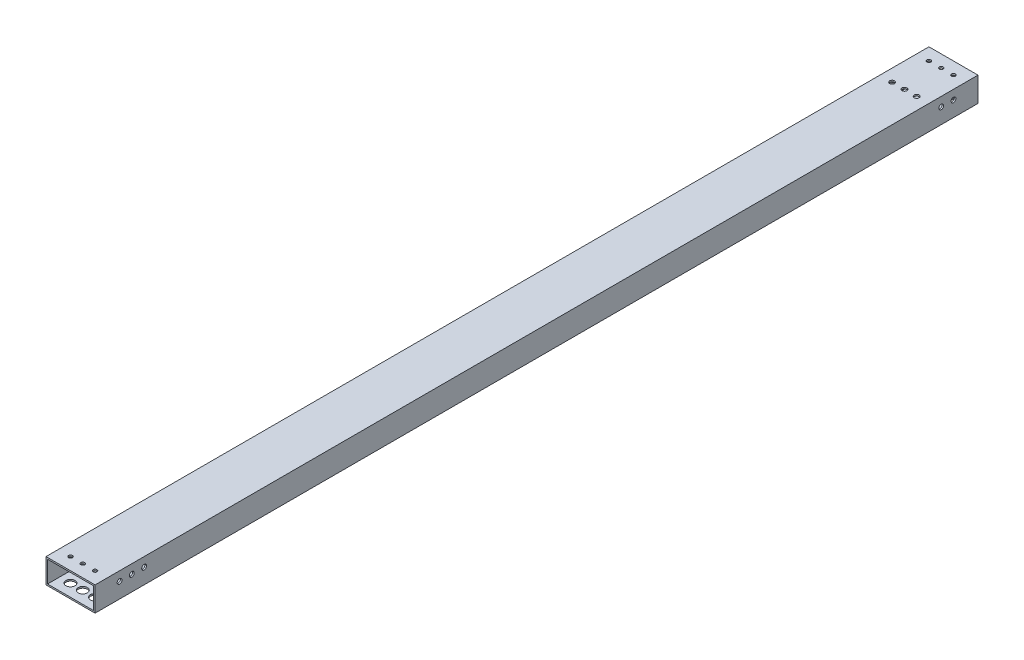
SolidWorks part; units mm, degrees
other "Markup1"
sketch "Sketch5" plane through (-25.4, -12.7, -457.2) normal (-0.35, -0.9329, -0.0852) x (-0.8023, 0.2515, 0.5413)
sketch "Sketch6" plane through (-25.4, -12.7, -457.2) normal (-0.35, -0.9329, -0.0852) x (-0.8023, 0.2515, 0.5413)
sketch "Sketch8" plane through (-25.4, -12.7, -457.2) normal (-0.35, -0.9329, -0.0852) x (-0.8023, 0.2515, 0.5413)
sketch "Sketch9" plane through (-25.4, -12.7, -457.2) normal (-0.35, -0.9329, -0.0852) x (-0.8023, 0.2515, 0.5413)
sketch "Sketch11" plane through (-25.4, -12.7, -457.2) normal (-0.35, -0.9329, -0.0852) x (-0.8023, 0.2515, 0.5413)
sketch "Sketch13" plane through (-25.4, -12.7, -457.2) normal (-0.35, -0.9329, -0.0852) x (-0.8023, 0.2515, 0.5413)
material "6061-T6 (SS)"
ref_plane "Front Plane" through (0, 0, 0) normal (0, 0, 1) x (1, 0, 0)
ref_plane "Top Plane" through (0, 0, 0) normal (0, 1, 0) x (1, 0, 0)
ref_plane "Right Plane" through (0, 0, 0) normal (1, 0, 0) x (0, 0, -1)
sketch "Sketch1" plane through (0, 0, 0) normal (0, 0, 1) x (1, 0, 0)
  line L0 (-23.8125, 11.1125) -> (23.8125, 11.1125)
  line L1 (-25.4, -12.7) -> (25.4, -12.7)
  line L2 (-25.4, -12.7) -> (-25.4, 12.7)
  line L3 (-25.4, 12.7) -> (25.4, 12.7)
  line L4 (25.4, -12.7) -> (25.4, 12.7)
  line L5 (-25.4, -12.7) -> (25.4, 12.7) construction
  line L6 (-25.4, 12.7) -> (25.4, -12.7) construction
  line L7 (23.8125, -11.1125) -> (23.8125, 11.1125)
  line L8 (-23.8125, -11.1125) -> (23.8125, -11.1125)
  line L9 (-23.8125, -11.1125) -> (-23.8125, 11.1125)
  point P0 (0, 0)
  dimension "D1" = 50.8
  dimension "D2" = 25.4
  dimension "D3" = 1.5875
extrude "Boss-Extrude1" add sketch "Sketch1" along normal mid plane 914.4
sketch "Sketch3" plane through (0, 12.7, 0) normal (0, 1, 0) x (1, 0, 0)
  line L2 (25.4, -457.2) -> (-25.4, -457.2) construction
  line L3 (25.4, 0) -> (-25.4, 0) construction
  line L4 (25.4, -457.2) -> (25.4, 457.2) construction
  line L5 (-25.4, -457.2) -> (-25.4, 457.2) construction
  circle A0 centre (0, -444.5) radius 2.0193
  circle A1 centre (12.7, -444.5) radius 2.0193
  circle A2 centre (-12.7, -444.5) radius 2.0193
  circle A3 centre (12.7, 444.5) radius 2.0193
  circle A4 centre (0, 444.5) radius 2.0193
  circle A5 centre (-12.7, 444.5) radius 2.0193
  dimension "D1" = 4.0386
  dimension "D2" = 12.7
  dimension "D3" = 12.7
  dimension "D4" = 12.7
extrude "Cut-Extrude2" cut sketch "Sketch3" against normal up to surface (1.5875 mm away) up to face at (0, 11.1125, 0)
sketch "Sketch4" plane through (0, -12.7, 0) normal (0, -1, 0) x (1, 0, 0)
  circle A0 centre (-12.7, 444.5) radius 2.0193 construction
  circle A1 centre (0, 444.5) radius 2.0193 construction
  circle A2 centre (12.7, 444.5) radius 2.0193 construction
  circle A3 centre (-12.7, 444.5) radius 2.0193
  circle A4 centre (0, 444.5) radius 2.0193
  circle A5 centre (12.7, 444.5) radius 2.0193
  circle A6 centre (-12.7, -444.5) radius 2.0193 construction
  circle A7 centre (0, -444.5) radius 2.0193 construction
  circle A8 centre (12.7, -444.5) radius 2.0193 construction
  circle A9 centre (-12.7, -444.5) radius 2.0193
  circle A10 centre (0, -444.5) radius 2.0193
  circle A11 centre (12.7, -444.5) radius 2.0193
  circle A12 centre (-12.7, 444.5) radius 4.7625
  circle A13 centre (0, 444.5) radius 4.7625
  circle A14 centre (12.7, 444.5) radius 4.7625
  circle A15 centre (-12.7, -444.5) radius 4.7625
  circle A16 centre (0, -444.5) radius 4.7625
  circle A17 centre (12.7, -444.5) radius 4.7625
  dimension "D1" = 9.525
  dimension "D2" = 9.525
extrude "Cut-Extrude4" cut sketch "Sketch4" against normal up to surface (1.5875 mm away) contours A12 A3 | A13 A4 | A4 | A3 | A5 | A14 A5 | A11 | A17 A11 | A16 A10 | A10 | A15 A9 | A9 region at (-12.7, -12.7, 444.5) region at (0, -12.7, 444.5) region at (12.7, -12.7, 444.5) region at (-12.7, -12.7, -444.5) region at (0, -12.7, -444.5) region at (12.7, -12.7, -444.5) region at (-17.3278, -12.7, 444.5) region at (-4.6278, -12.7, 444.5) region at (8.0722, -12.7, 444.5) region at (-17.3278, -12.7, -444.5) region at (-4.6278, -12.7, -444.5) region at (8.0722, -12.7, -444.5) up to face at (0, -11.1125, 0)
sketch "Sketch7" plane through (25.4, 0, 0) normal (1, 0, 0) x (0, 0, -1)
  line L0 (-457.2, -12.7) -> (-457.2, 12.7) construction
  line L1 (-457.2, 12.7) -> (457.2, 12.7) construction
  line L2 (0, 12.7) -> (0, -12.7) construction
  line L3 (-457.2, -12.7) -> (457.2, -12.7) construction
  circle A0 centre (-444.5, 3.175) radius 2.4892
  circle A1 centre (-431.8, 3.175) radius 2.4892
  circle A2 centre (-419.1, 3.175) radius 2.4892
  circle A3 centre (-406.4, 3.175) radius 2.4892
  circle A4 centre (406.4, 3.175) radius 2.4892
  circle A5 centre (419.1, 3.175) radius 2.4892
  circle A6 centre (431.8, 3.175) radius 2.4892
  circle A7 centre (444.5, 3.175) radius 2.4892
  dimension "D3" = 4.9784
  dimension "D1" = 12.7
  dimension "D2" = 9.525
  dimension "D4" = 12.7
  dimension "D5" = 12.7
  dimension "D6" = 12.7
extrude "Cut-Extrude5" cut sketch "Sketch7" against normal through all contours A5 | A6 | A1 | A2 | A3 region at (25.4, 3.175, 431.8) region at (25.4, 3.175, 419.1) region at (25.4, 3.175, 406.4) region at (25.4, 3.175, -419.1) region at (25.4, 3.175, -431.8)
sketch "Sketch10" plane through (0, 12.7, 0) normal (0, 1, 0) x (1, 0, 0)
  line L0 (25.4, 457.2) -> (-25.4, 457.2) construction
  circle A0 centre (-12.7, 406.4) radius 2.5527
  circle A1 centre (0, 406.4) radius 2.5527
  circle A2 centre (12.7, 406.4) radius 2.5527
  dimension "D1" = 5.1054
  dimension "D2" = 12.7
  dimension "D3" = 12.7
  dimension "D4" = 50.8
extrude "Cut-Extrude6" cut sketch "Sketch10" against normal through all
